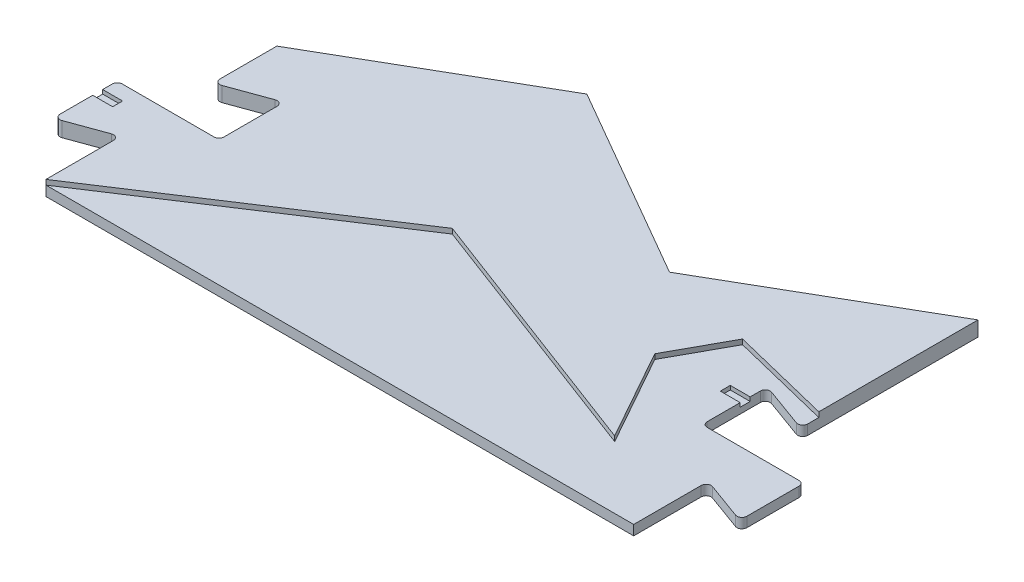
SolidWorks part; units mm, degrees
ref_plane "Přední rovina" through (0, 0, 0) normal (0, 0, 1) x (1, 0, 0)
ref_plane "Horní rovina" through (0, 0, 0) normal (0, 1, 0) x (1, 0, 0)
ref_plane "Pravá rovina" through (0, 0, 0) normal (1, 0, 0) x (0, 0, -1)
sketch "Skica1" plane through (0, 0, 0) normal (0, 1, 0) x (1, 0, 0)
  line L8 (-118.1438, 0) -> (-118.1438, 15)
  line L10 (-118.1438, 15) -> (-128.0938, 11.3785)
  line L11 (-128.0938, 11.3785) -> (-128.0938, 24.2785)
  line L12 (-107.6438, 24.2785) -> (-107.6438, 37.3785)
  line L13 (-107.6438, 37.3785) -> (-118.1432, 33.557)
  line L17 (-118.1432, 33.557) -> (-118.1432, 46.41)
  line L18 (-118.1432, 46.41) -> (-78.6351, 69.22)
  line L19 (-78.6351, 69.22) -> (-39.3176, 46.52)
  line L20 (-118.1438, 15) -> (-118.1438, 56.5658) construction
  line L21 (-107.6438, 24.2785) -> (-128.0938, 24.2785)
  line L22 (-68.7793, 32.3134) -> (-118.1438, 0)
  line L23 (-68.7793, 32.3134) -> (-16.3273, 12.5112)
  line L24 (-16.3273, 12.5112) -> (-26.5931, 30.831)
  line L25 (-26.5931, 30.831) -> (-20.3432, 42.23)
  line L26 (-39.3176, 46.52) -> (0, 69.22)
  line L28 (-118.1438, 0) -> (0, 0)
  line L29 (-20.3432, 42.23) -> (0, 37.22)
  line L30 (0, 0) -> (0, 15)
  line L33 (0, 69.22) -> (0, 0) construction
  line L34 (-10.5, 24.2783) -> (9.9505, 24.2783)
  line L39 (0, 69.22) -> (0, 33.5566)
  line L40 (0, 15) -> (9.9505, 11.3783)
  line L41 (9.9505, 24.2783) -> (9.9505, 11.3783)
  line L42 (0, 33.5566) -> (-10.5, 37.3783)
  line L43 (-10.5, 37.3783) -> (-10.5, 24.2783)
  point P27 (-0.2747, 24.2783)
  dimension "D1" = 45.4
  dimension "D2" = 45.62
  dimension "D3" = 120
  dimension "D4" = 70
  dimension "D5" = 12.9
  dimension "D6" = 13.1
  dimension "D7" = 70
  dimension "D8" = 10.5
  dimension "D9" = 15
  dimension "D10" = 122
  dimension "D11" = 13
  dimension "D12" = 21
  dimension "D13" = 56.0655
  dimension "D14" = 120
  dimension "D15" = 59
  dimension "D16" = 45.4
  dimension "D17" = 120
  dimension "D18" = 118.1438
  dimension "D19" = 104.9
  dimension "D20" = 32.3134
  dimension "D21" = 70
  dimension "D22" = 13.1
  dimension "D23" = 70
  dimension "D24" = 10.5
  dimension "D25" = 15
  dimension "D26" = 12.5112
  dimension "D27" = 69.22
  dimension "D28" = 32
  dimension "D29" = 12.9
  dimension "D30" = 69.22
  dimension "D31" = 9.95
extrude "Přidat vysunutím1" add sketch "Skica1" along normal blind 3 contours L20 L23 L24 L25 L29 L39 L26 L19 L18 L17 L13 L12 L21 | L10 L20 L21 L11 region at (-66.762, 0, -39.2146)
extrude "Přidat vysunutím2" add sketch "Skica1<5>" along normal blind 2 contours L43 L42 L39 L29 L25 L24 L23 L8 L28 L30 L40 L41 L34 region at (-46.7963, 0, -13.9892)
sketch "Skica1<5>" plane through (0, 0, 0) normal (0, 1, 0) x (1, 0, 0) same geometry as "Skica1"
fillet "Zaoblit4" radius 1 12 edges at (0, 1, -33.5566) (-10.5, 1, -24.2783) (-10.5, 1, -37.3783) (0, 1, -15) (9.9505, 1, -11.3783) (9.9505, 1, -24.2783) (-128.0938, 1.5, -11.3785) (-128.0938, 1.5, -24.2785) (-107.6438, 1.5, -24.2785) (-107.6438, 1.5, -37.3785) (-118.1432, 1.5, -33.557) (-118.1438, 1.5, -15)
sketch "Skica2" plane through (0, 3, 0) normal (0, 1, 0) x (1, 0, 0)
  line L10 (-128.0938, 18.0426) -> (-90.5805, 18.0426) construction
  line L11 (-128.0938, 12.8066) -> (-128.0938, 23.2785) construction
  line L12 (-68.7793, 32.3134) -> (-118.1438, 0) construction
  line L16 (-124.0938, 21.3426) -> (-128.0938, 21.3426)
  line L17 (-108.6438, 24.2785) -> (-127.0938, 24.2785) construction
  line L18 (-124.0938, 19.3426) -> (-124.0938, 21.3426)
  line L19 (-128.0938, 19.3426) -> (-124.0938, 19.3426)
  line L24 (-128.0938, 21.3426) -> (-128.0938, 19.3426)
  dimension "D4" = 2
  dimension "D5" = 4
  dimension "D6" = 1.3
sketch "Skica3" plane through (0, 2, 0) normal (0, 1, 0) x (1, 0, 0)
  line L2 (-16.3273, 12.5112) -> (-26.5931, 30.831) construction
  line L3 (-10.5, 30.6142) -> (-26.4717, 30.6142) construction
  line L4 (-10.5, 35.9502) -> (-10.5, 25.2783) construction
  line L5 (-10.5, 33.9142) -> (-14.5, 33.9142)
  line L6 (-14.5, 33.9142) -> (-14.5, 31.9142)
  line L7 (-14.5, 31.9142) -> (-10.5, 31.9142)
  line L17 (-10.5, 33.9142) -> (-10.5, 31.9142)
  dimension "D1" = 2
  dimension "D2" = 4
  dimension "D3" = 1.3
extrude "Odebrat vysunutím2" cut sketch "Skica2" against normal blind 0.8
extrude "Odebrat vysunutím3" cut sketch "Skica3" against normal blind 0.8
